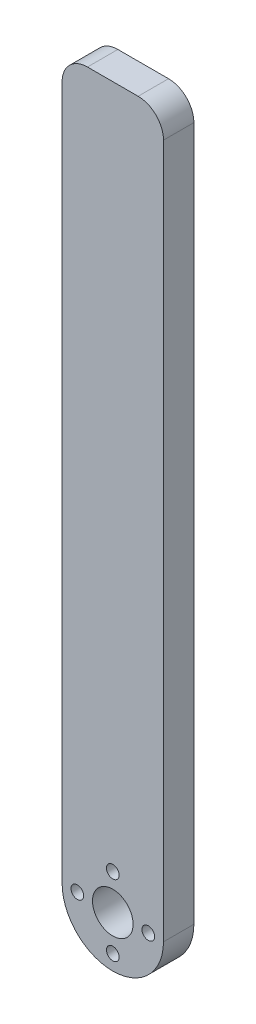
SolidWorks part; units mm, degrees
ref_plane "Front" through (0, 0, 0) normal (0, 0, 1) x (1, 0, 0)
ref_plane "Top" through (0, 0, 0) normal (0, 1, 0) x (1, 0, 0)
ref_plane "Right" through (0, 0, 0) normal (1, 0, 0) x (0, 0, -1)
sketch "Esquisse1" plane through (0, 0, 0) normal (0, 0, 1) x (1, 0, 0)
  line L1 (0, 0) -> (20, 0)
  line L2 (0, 0) -> (0, 152)
  line L3 (0, 152) -> (20, 152)
  line L4 (20, 0) -> (20, 152)
  dimension "D1" = 20
  dimension "D2" = 152
extrude "Boss.-Extru.1" add sketch "Esquisse1" along normal blind 6
sketch "Esquisse2" plane through (0, 0, 6) normal (0, 0, 1) x (1, 0, 0)
  line L0 (10, 0) -> (10, 10) construction
  line L1 (0, 0) -> (20, 0) construction
  line L2 (10, 10) -> (0, 10) construction
  line L3 (0, 152) -> (0, 0) construction
  circle A0 centre (10, 10) radius 4
  dimension "D2" = 8
  dimension "D1" = 10
extrude "Enlèv. mat.-Extru.1" cut sketch "Esquisse2" against normal through all both and the other way through all
fillet "Congé1" radius 10 2 edges at (20, 0, 3) (0, 0, 3)
fillet "Congé2" radius 5 2 edges at (20, 152, 3) (0, 152, 3)
sketch "Esquisse3" plane through (0, 0, 6) normal (0, 0, 1) x (1, 0, 0)
  line L0 (10, 17) -> (10, 10) construction
  circle A0 centre (10, 17) radius 1.25
  circle A1 centre (17, 10) radius 1.25
  circle A2 centre (10, 3) radius 1.25
  circle A3 centre (3, 10) radius 1.25
  point P12 (10, 10)
  dimension "D2" = 2.5
  dimension "D1" = 7
  dimension "D3" = 4
extrude "Enlèv. mat.-Extru.2" cut sketch "Esquisse3" against normal through all both and the other way through all
